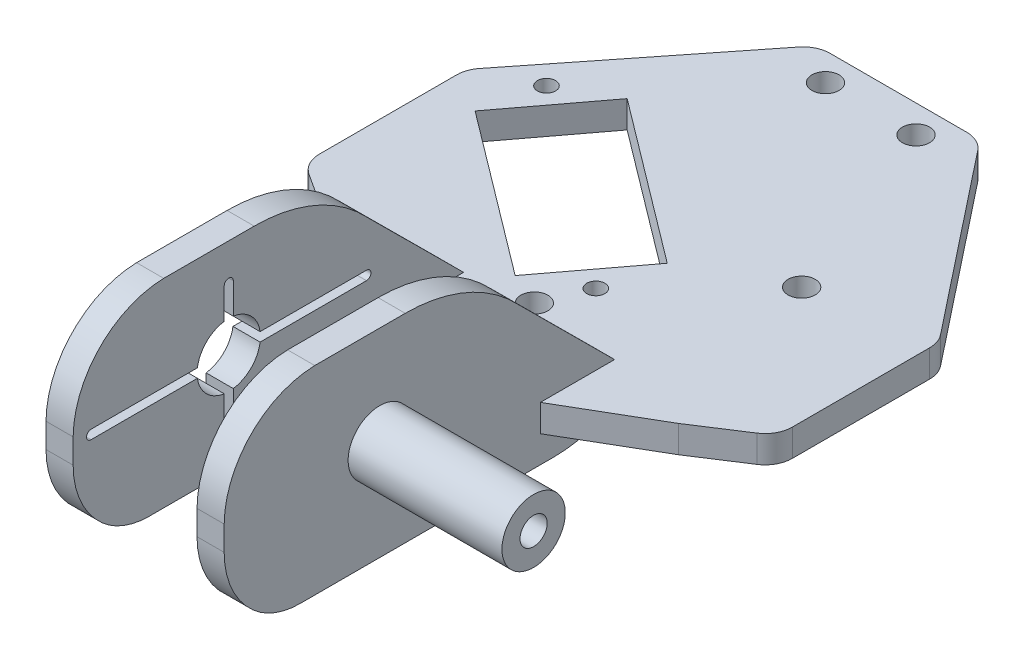
SolidWorks part; units mm, degrees
ref_plane "Front Plane" through (0, 0, 0) normal (0, 0, 1) x (1, 0, 0)
ref_plane "Top Plane" through (0, 0, 0) normal (0, 1, 0) x (1, 0, 0)
ref_plane "Right Plane" through (0, 0, 0) normal (1, 0, 0) x (0, 0, -1)
sketch "Sketch1" plane through (0, 0, 0) normal (0, 1, 0) x (1, 0, 0)
  line L7 (-4.1595, 37.5951) -> (4.2976, 37.5951)
  line L8 (-9.9025, 36.4566) -> (-20.3157, 23.2959) construction
  line L10 (0, 0) -> (0, -15.9475) construction
  line L12 (-9.9025, 36.4566) -> (-20.3157, 23.2959)
  line L15 (-20.9631, 21.4344) -> (-20.9631, -5.9026) construction
  line L16 (-19.4729, -6.2109) -> (-9.8452, -11.8182)
  line L19 (-9.8452, -11.8182) -> (-9.8452, -21.8182)
  line L22 (-9.8452, -21.8182) -> (-6.8452, -21.8182)
  line L23 (-6.8452, -21.8182) -> (-6.8452, -12.4305)
  line L24 (-6.8452, -12.4305) -> (6.8452, -12.4305)
  line L25 (-4.1595, 37.5951) -> (-7.5499, 37.5951)
  line L26 (4.1595, 37.5951) -> (1.3957, 42.8144)
  line L27 (1.3957, 42.8144) -> (0, 43.4367)
  line L28 (24.762, -2.7815) -> (19.4729, -6.2109)
  line L29 (26.1299, 14.9044) -> (26.1299, -0.2643)
  line L30 (18.8536, 25.1438) -> (25.4825, 16.7659)
  line L31 (-18.8536, 25.1438) -> (-25.4825, 16.7659)
  line L32 (-26.1299, 14.9044) -> (-26.1299, -0.2643)
  line L33 (-24.762, -2.7815) -> (-19.4729, -6.2109)
  line L34 (4.1595, 37.5951) -> (7.5499, 37.5951)
  line L35 (6.8452, -21.8182) -> (6.8452, -12.4305)
  line L36 (9.8452, -21.8182) -> (6.8452, -21.8182)
  line L37 (9.8452, -11.8182) -> (9.8452, -21.8182)
  line L38 (19.4729, -6.2109) -> (9.8452, -11.8182)
  line L39 (0, 0) -> (0, 47.8638) construction
  line L40 (-1.3957, 42.8144) -> (0, 43.4367)
  line L41 (-4.1595, 37.5951) -> (-1.3957, 42.8144)
  line L42 (9.9025, 36.4566) -> (20.3157, 23.2959)
  arc A1 (-7.5499, 37.5951) -> (-9.9025, 36.4566) centre (-7.5499, 34.5951) ccw construction
  circle A4 centre (-5.0017, 34.5359) radius 1.5 construction
  circle A8 centre (-5.0017, 34.5359) radius 1.5
  arc A11 (-7.5499, 37.5951) -> (-9.9025, 36.4566) centre (-7.5499, 34.5951) ccw
  arc A12 (-19.7137, -6.0547) -> (-19.4729, -6.2109) centre (-17.9631, -3.6185) ccw
  arc A14 (25.4825, 16.7659) -> (26.1299, 14.9044) centre (23.1299, 14.9044) cw
  arc A15 (26.1299, -0.2643) -> (24.762, -2.7815) centre (23.1299, -0.2643) cw
  arc A16 (19.7137, -6.0547) -> (19.4729, -6.2109) centre (17.9631, -3.6185) cw
  arc A17 (-26.1299, -0.2643) -> (-24.762, -2.7815) centre (-23.1299, -0.2643) ccw
  arc A18 (-25.4825, 16.7659) -> (-26.1299, 14.9044) centre (-23.1299, 14.9044) ccw
  arc A19 (7.5499, 37.5951) -> (9.9025, 36.4566) centre (7.5499, 34.5951) cw
  circle A20 centre (5.0017, 34.5359) radius 1.5
  point P28 (0.1548, -12.4305)
  point P33 (-20.9631, -5.343)
  point P37 (0, -12.4305)
  point P41 (0.1548, -12.4305)
  point P46 (26.1299, 15.9477)
  point P48 (26.1299, -1.8946)
  point P49 (-0.1548, -12.4305)
  point P50 (20.9631, -5.343)
  point P54 (-26.1299, -1.8946)
  point P57 (-26.1299, 15.9477)
  dimension "D1" = 3
  dimension "D3" = 3
  dimension "D4" = 10
extrude "Boss-Extrude2" add sketch "Sketch1" along normal blind 3 contours A11 L12 A12 L16 L19 L22 L23 A8 region at (0, 0, -10.32)
mirror "Mirror1" about plane through (0, 0, 0) normal (1, 0, 0) of "Boss-Extrude2"
sketch "Sketch3" plane through (9.8452, 0, 0) normal (1, 0, 0) x (0, 0, -1)
  line L0 (0, 0) -> (-5.4214, -2.0662)
  line L1 (-10.362, -2.9757) -> (-38.362, -2.9757)
  line L2 (-46.7647, 6.1171) -> (-46.7647, 8.8248)
  line L3 (-36.7549, 18.9944) -> (-26.7549, 18.9944)
  line L4 (-14.3131, 13.6377) -> (-3.6185, 3)
  line L5 (-3.6185, 3) -> (0, 0)
  line L6 (-11.8182, 3) -> (-11.8182, 0) construction
  arc A0 (-5.4214, -2.0662) -> (-10.362, -2.9757) centre (-10.362, 10.8976) cw
  arc A1 (-38.362, -2.9757) -> (-43.5481, -1.0139) centre (-38.362, 4.8597) cw
  arc A2 (-43.5481, -1.0139) -> (-46.7647, 6.1171) centre (-37.2518, 6.1171) cw
  circle A5 centre (-29.5682, 8.0684) radius 5 construction
  arc A7 (-26.7549, 18.9944) -> (-14.3131, 13.6377) centre (-26.7549, 1.8671) cw
  arc A8 (-36.7549, 18.9944) -> (-46.7647, 8.8248) centre (-36.4897, 8.7223) ccw
  dimension "D1" = 10
  dimension "D2" = 17.75
  dimension "D3" = 28
  dimension "D4" = 10
extrude "Boss-Extrude3" add sketch "Sketch3" against normal blind 3
sketch "Sketch4" plane through (9.8452, 0, 0) normal (1, 0, 0) x (0, 0, -1)
  circle A0 centre (-29.5682, 8.0684) radius 5
mirror "Mirror2" about plane through (0, 0, 0) normal (1, 0, 0) of "Boss-Extrude3"
extrude "Cut-Extrude1" cut sketch "Sketch4" against normal up to surface (3 mm away) rebuild error yes
sketch "Sketch5" plane through (-9.8452, 0, 0) normal (-1, 0, 0) x (0, 0, 1)
  line L0 (14.3482, 8.0684) -> (44.7882, 8.0684) construction
  line L1 (14.3482, 8.5684) -> (44.7882, 8.5684)
  line L2 (14.3482, 7.5684) -> (44.7882, 7.5684)
  line L3 (29.5682, 1.2134) -> (29.5682, 14.9234) construction
  line L4 (29.0682, 1.2134) -> (29.0682, 14.9234)
  line L5 (30.0682, 1.2134) -> (30.0682, 14.9234)
  circle A0 centre (29.5682, 8.0684) radius 5 construction
  circle A1 centre (29.5682, 8.0684) radius 5 construction
  arc A2 (14.3482, 8.5684) -> (14.3482, 7.5684) centre (14.3482, 8.0684) ccw
  arc A3 (44.7882, 7.5684) -> (44.7882, 8.5684) centre (44.7882, 8.0684) ccw
  arc A4 (29.0682, 1.2134) -> (30.0682, 1.2134) centre (29.5682, 1.2134) ccw
  arc A5 (30.0682, 14.9234) -> (29.0682, 14.9234) centre (29.5682, 14.9234) ccw
  circle A6 centre (29.5682, 8.0684) radius 3.5
  point P5 (29.5682, 8.0684)
  point P11 (29.5682, 8.0684)
  dimension "D1" = 0.5
  dimension "D2" = 0.5
  dimension "D5" = 10
  dimension "D6" = 7
  dimension "D3" = 30.44
  dimension "D4" = 13.71
extrude "Cut-Extrude2" cut sketch "Sketch5" against normal blind 3 contours L5 A6 L2 | L2 A6 L4 | L4 A6 L1 | L1 A6 L5 | L2 A3 L1 A2 | L5 A4 L4 A5 region at (-9.8452, 9.7725, 27.8641) region at (-9.8452, 6.3644, 27.8641) region at (-9.8452, 9.7725, 31.2723) region at (-9.8452, 6.3644, 31.2723)
sketch "Sketch7" plane through (0, 3, 0) normal (0, 1, 0) x (1, 0, 0)
  line L0 (-14.4326, 22.0478) -> (3.5367, 8.507)
  line L1 (3.5367, 8.507) -> (-3.6851, -1.0766)
  line L2 (-3.6851, -1.0766) -> (-21.6544, 12.4642)
  line L3 (-21.6544, 12.4642) -> (-14.4326, 22.0478)
  line L26 (-6.8452, -3.6185) -> (-6.8452, -12.4305)
  line L27 (-6.8452, -3.6185) -> (-6.8452, -12.4305)
  line L42 (6.8452, -3.6185) -> (9.8452, -3.6185)
  line L43 (6.8452, -3.6185) -> (9.8452, -3.6185)
  line L44 (-9.9025, 36.4566) -> (-25.4825, 16.7659)
  line L45 (-9.9025, 36.4566) -> (-25.4825, 16.7659)
  line L46 (-19.4729, -6.2109) -> (-9.8452, -11.8182)
  line L47 (-19.4729, -6.2109) -> (-9.8452, -11.8182)
  line L48 (-9.8452, -11.8182) -> (-9.8452, -3.6185)
  line L50 (-9.8452, -11.8182) -> (-9.8452, -3.6185)
  line L52 (-24.762, -2.7815) -> (-19.4729, -6.2109)
  line L53 (-24.762, -2.7815) -> (-19.4729, -6.2109)
  line L54 (-9.8452, -3.6185) -> (-6.8452, -3.6185)
  line L55 (-9.8452, -3.6185) -> (-6.8452, -3.6185)
  line L56 (-26.1299, 14.9044) -> (-26.1299, -0.2643)
  line L57 (-26.1299, 14.9044) -> (-26.1299, -0.2643)
  line L62 (7.5499, 37.5951) -> (-7.5499, 37.5951)
  line L64 (7.5499, 37.5951) -> (-7.5499, 37.5951)
  line L66 (-6.8452, -12.4305) -> (6.8452, -12.4305)
  line L68 (-6.8452, -12.4305) -> (6.8452, -12.4305)
  line L70 (6.8452, -12.4305) -> (6.8452, -3.6185)
  line L72 (6.8452, -12.4305) -> (6.8452, -3.6185)
  line L74 (9.8452, -3.6185) -> (9.8452, -11.8182)
  line L76 (9.8452, -3.6185) -> (9.8452, -11.8182)
  line L78 (9.8452, -11.8182) -> (19.4729, -6.2109)
  line L80 (9.8452, -11.8182) -> (19.4729, -6.2109)
  line L82 (19.4729, -6.2109) -> (24.762, -2.7815)
  line L83 (19.4729, -6.2109) -> (24.762, -2.7815)
  line L84 (26.1299, -0.2643) -> (26.1299, 14.9044)
  line L85 (26.1299, -0.2643) -> (26.1299, 14.9044)
  line L86 (25.4825, 16.7659) -> (9.9025, 36.4566)
  line L87 (25.4825, 16.7659) -> (9.9025, 36.4566)
  circle A0 centre (-20.1199, 18.8207) radius 1
  circle A1 centre (2.0023, 2.1505) radius 1
  arc A3 (-7.5499, 37.5951) -> (-9.9025, 36.4566) centre (-7.5499, 34.5951) ccw
  arc A18 (-7.5499, 37.5951) -> (-9.9025, 36.4566) centre (-7.5499, 34.5951) ccw
  arc A19 (-25.4825, 16.7659) -> (-26.1299, 14.9044) centre (-23.1299, 14.9044) ccw
  arc A20 (-25.4825, 16.7659) -> (-26.1299, 14.9044) centre (-23.1299, 14.9044) ccw
  arc A22 (-26.1299, -0.2643) -> (-24.762, -2.7815) centre (-23.1299, -0.2643) ccw
  arc A24 (-26.1299, -0.2643) -> (-24.762, -2.7815) centre (-23.1299, -0.2643) ccw
  arc A25 (24.762, -2.7815) -> (26.1299, -0.2643) centre (23.1299, -0.2643) ccw
  arc A26 (24.762, -2.7815) -> (26.1299, -0.2643) centre (23.1299, -0.2643) ccw
  arc A27 (26.1299, 14.9044) -> (25.4825, 16.7659) centre (23.1299, 14.9044) ccw
  arc A28 (26.1299, 14.9044) -> (25.4825, 16.7659) centre (23.1299, 14.9044) ccw
  arc A29 (9.9025, 36.4566) -> (7.5499, 37.5951) centre (7.5499, 34.5951) ccw
  arc A30 (9.9025, 36.4566) -> (7.5499, 37.5951) centre (7.5499, 34.5951) ccw
  dimension "D2" = 12
  dimension "D3" = 22.5
  dimension "D1" = 0
sketch "Sketch8" plane through (0, 3, 0) normal (0, 1, 0) x (1, 0, 0)
  line L0 (-14.4326, 22.0478) -> (3.5367, 8.507) construction
  line L1 (3.5367, 8.507) -> (-3.6851, -1.0766) construction
  line L2 (-3.6851, -1.0766) -> (-21.6544, 12.4642) construction
  line L3 (-21.6544, 12.4642) -> (-14.4326, 22.0478) construction
  line L4 (-14.4326, 22.0478) -> (3.5367, 8.507)
  line L5 (3.5367, 8.507) -> (-3.6851, -1.0766)
  line L6 (-3.6851, -1.0766) -> (-21.6544, 12.4642)
  line L7 (-21.6544, 12.4642) -> (-14.4326, 22.0478)
  line L28 (-24.762, -2.7815) -> (-19.4729, -6.2109)
  line L30 (-6.8452, -3.6185) -> (-6.8452, -12.4305)
  line L31 (-6.8452, -3.6185) -> (-6.8452, -12.4305)
  line L44 (-24.762, -2.7815) -> (-19.4729, -6.2109)
  line L48 (6.8452, -3.6185) -> (9.8452, -3.6185)
  line L49 (6.8452, -3.6185) -> (9.8452, -3.6185)
  line L50 (-9.9025, 36.4566) -> (-25.4825, 16.7659)
  line L51 (-9.9025, 36.4566) -> (-25.4825, 16.7659)
  line L52 (-26.1299, 14.9044) -> (-26.1299, -0.2643)
  line L53 (-26.1299, 14.9044) -> (-26.1299, -0.2643)
  line L54 (-19.4729, -6.2109) -> (-9.8452, -11.8182)
  line L55 (-19.4729, -6.2109) -> (-9.8452, -11.8182)
  line L56 (-9.8452, -11.8182) -> (-9.8452, -3.6185)
  line L57 (-9.8452, -11.8182) -> (-9.8452, -3.6185)
  line L58 (-9.8452, -3.6185) -> (-6.8452, -3.6185)
  line L59 (-9.8452, -3.6185) -> (-6.8452, -3.6185)
  line L64 (7.5499, 37.5951) -> (-7.5499, 37.5951)
  line L66 (7.5499, 37.5951) -> (-7.5499, 37.5951)
  line L68 (-6.8452, -12.4305) -> (6.8452, -12.4305)
  line L70 (-6.8452, -12.4305) -> (6.8452, -12.4305)
  line L72 (6.8452, -12.4305) -> (6.8452, -3.6185)
  line L74 (6.8452, -12.4305) -> (6.8452, -3.6185)
  line L76 (9.8452, -3.6185) -> (9.8452, -11.8182)
  line L78 (9.8452, -3.6185) -> (9.8452, -11.8182)
  line L80 (9.8452, -11.8182) -> (19.4729, -6.2109)
  line L82 (9.8452, -11.8182) -> (19.4729, -6.2109)
  line L84 (19.4729, -6.2109) -> (24.762, -2.7815)
  line L85 (19.4729, -6.2109) -> (24.762, -2.7815)
  line L86 (26.1299, -0.2643) -> (26.1299, 14.9044)
  line L87 (26.1299, -0.2643) -> (26.1299, 14.9044)
  line L88 (25.4825, 16.7659) -> (9.9025, 36.4566)
  line L89 (25.4825, 16.7659) -> (9.9025, 36.4566)
  circle A0 centre (-20.1199, 18.8207) radius 1 construction
  circle A1 centre (2.0023, 2.1505) radius 1 construction
  circle A2 centre (-20.1199, 18.8207) radius 1
  circle A3 centre (2.0023, 2.1505) radius 1
  arc A5 (-7.5499, 37.5951) -> (-9.9025, 36.4566) centre (-7.5499, 34.5951) ccw
  arc A18 (-7.5499, 37.5951) -> (-9.9025, 36.4566) centre (-7.5499, 34.5951) ccw
  arc A19 (-25.4825, 16.7659) -> (-26.1299, 14.9044) centre (-23.1299, 14.9044) ccw
  arc A20 (-25.4825, 16.7659) -> (-26.1299, 14.9044) centre (-23.1299, 14.9044) ccw
  arc A21 (-26.1299, -0.2643) -> (-24.762, -2.7815) centre (-23.1299, -0.2643) ccw
  arc A22 (-26.1299, -0.2643) -> (-24.762, -2.7815) centre (-23.1299, -0.2643) ccw
  arc A23 (24.762, -2.7815) -> (26.1299, -0.2643) centre (23.1299, -0.2643) ccw
  arc A24 (24.762, -2.7815) -> (26.1299, -0.2643) centre (23.1299, -0.2643) ccw
  arc A25 (26.1299, 14.9044) -> (25.4825, 16.7659) centre (23.1299, 14.9044) ccw
  arc A26 (26.1299, 14.9044) -> (25.4825, 16.7659) centre (23.1299, 14.9044) ccw
  arc A27 (9.9025, 36.4566) -> (7.5499, 37.5951) centre (7.5499, 34.5951) ccw
  arc A28 (9.9025, 36.4566) -> (7.5499, 37.5951) centre (7.5499, 34.5951) ccw
  dimension "D1" = 0
sketch "Sketch9" plane through (0, 3, 0) normal (0, 1, 0) x (1, 0, 0)
  line L0 (3.5367, 8.507) -> (-3.6851, -1.0766) construction
  line L1 (-14.4326, 22.0478) -> (3.5367, 8.507) construction
  line L2 (-3.6851, -1.0766) -> (-21.6544, 12.4642) construction
  line L3 (-21.6544, 12.4642) -> (-14.4326, 22.0478) construction
  line L4 (3.5367, 8.507) -> (-3.6851, -1.0766)
  line L5 (-14.4326, 22.0478) -> (3.5367, 8.507)
  line L6 (-3.6851, -1.0766) -> (-21.6544, 12.4642)
  line L7 (-21.6544, 12.4642) -> (-14.4326, 22.0478)
  line L28 (-24.762, -2.7815) -> (-19.4729, -6.2109)
  line L30 (-6.8452, -3.6185) -> (-6.8452, -12.4305)
  line L31 (-6.8452, -3.6185) -> (-6.8452, -12.4305)
  line L44 (-24.762, -2.7815) -> (-19.4729, -6.2109)
  line L48 (6.8452, -3.6185) -> (9.8452, -3.6185)
  line L49 (6.8452, -3.6185) -> (9.8452, -3.6185)
  line L50 (-9.9025, 36.4566) -> (-25.4825, 16.7659)
  line L51 (-26.1299, 14.9044) -> (-26.1299, -0.2643)
  line L52 (-19.4729, -6.2109) -> (-9.8452, -11.8182)
  line L53 (-19.4729, -6.2109) -> (-9.8452, -11.8182)
  line L54 (-9.8452, -11.8182) -> (-9.8452, -3.6185)
  line L55 (-9.8452, -11.8182) -> (-9.8452, -3.6185)
  line L56 (-9.8452, -3.6185) -> (-6.8452, -3.6185)
  line L57 (-9.8452, -3.6185) -> (-6.8452, -3.6185)
  line L62 (7.5499, 37.5951) -> (-7.5499, 37.5951)
  line L63 (7.5499, 37.5951) -> (-7.5499, 37.5951)
  line L64 (-6.8452, -12.4305) -> (6.8452, -12.4305)
  line L65 (-6.8452, -12.4305) -> (6.8452, -12.4305)
  line L66 (6.8452, -12.4305) -> (6.8452, -3.6185)
  line L67 (6.8452, -12.4305) -> (6.8452, -3.6185)
  line L68 (9.8452, -3.6185) -> (9.8452, -11.8182)
  line L69 (9.8452, -3.6185) -> (9.8452, -11.8182)
  line L70 (9.8452, -11.8182) -> (19.4729, -6.2109)
  line L71 (9.8452, -11.8182) -> (19.4729, -6.2109)
  line L72 (19.4729, -6.2109) -> (24.762, -2.7815)
  line L73 (19.4729, -6.2109) -> (24.762, -2.7815)
  line L74 (26.1299, -0.2643) -> (26.1299, 14.9044)
  line L75 (26.1299, -0.2643) -> (26.1299, 14.9044)
  line L76 (25.4825, 16.7659) -> (9.9025, 36.4566)
  line L77 (25.4825, 16.7659) -> (9.9025, 36.4566)
  circle A0 centre (2.0023, 2.1505) radius 1 construction
  circle A1 centre (-20.1199, 18.8207) radius 1 construction
  circle A2 centre (2.0023, 2.1505) radius 1
  circle A4 centre (-20.1199, 18.8207) radius 1
  arc A6 (-7.5499, 37.5951) -> (-9.9025, 36.4566) centre (-7.5499, 34.5951) ccw
  arc A21 (-7.5499, 37.5951) -> (-9.9025, 36.4566) centre (-7.5499, 34.5951) ccw
  arc A22 (-25.4825, 16.7659) -> (-26.1299, 14.9044) centre (-23.1299, 14.9044) ccw
  arc A23 (-26.1299, -0.2643) -> (-24.762, -2.7815) centre (-23.1299, -0.2643) ccw
  arc A24 (-26.1299, -0.2643) -> (-24.762, -2.7815) centre (-23.1299, -0.2643) ccw
  arc A25 (24.762, -2.7815) -> (26.1299, -0.2643) centre (23.1299, -0.2643) ccw
  arc A26 (24.762, -2.7815) -> (26.1299, -0.2643) centre (23.1299, -0.2643) ccw
  arc A27 (26.1299, 14.9044) -> (25.4825, 16.7659) centre (23.1299, 14.9044) ccw
  arc A28 (26.1299, 14.9044) -> (25.4825, 16.7659) centre (23.1299, 14.9044) ccw
  arc A29 (9.9025, 36.4566) -> (7.5499, 37.5951) centre (7.5499, 34.5951) ccw
  arc A30 (9.9025, 36.4566) -> (7.5499, 37.5951) centre (7.5499, 34.5951) ccw
  dimension "D1" = 0
sketch "Sketch10" plane through (0, 3, 0) normal (0, 1, 0) x (1, 0, 0)
  line L16 (-6.8452, -3.6185) -> (-6.8452, -12.4305)
  line L17 (-6.8452, -12.4305) -> (6.8452, -12.4305)
  line L18 (6.8452, -12.4305) -> (6.8452, -3.6185)
  line L19 (6.8452, -3.6185) -> (9.8452, -3.6185)
  line L20 (9.8452, -3.6185) -> (9.8452, -11.8182)
  line L21 (9.8452, -11.8182) -> (19.4729, -6.2109)
  line L22 (19.4729, -6.2109) -> (24.762, -2.7815)
  line L23 (26.1299, -0.2643) -> (26.1299, 14.9044)
  line L24 (25.4825, 16.7659) -> (9.9025, 36.4566)
  line L25 (7.5499, 37.5951) -> (-7.5499, 37.5951)
  line L26 (-9.9025, 36.4566) -> (-25.4825, 16.7659)
  line L27 (-26.1299, 14.9044) -> (-26.1299, -0.2643)
  line L28 (-24.762, -2.7815) -> (-19.4729, -6.2109)
  line L29 (-19.4729, -6.2109) -> (-9.8452, -11.8182)
  line L30 (-9.8452, -11.8182) -> (-9.8452, -3.6185)
  line L31 (-9.8452, -3.6185) -> (-6.8452, -3.6185)
  line L32 (-6.8452, -3.6185) -> (-6.8452, -12.4305)
  line L33 (-6.8452, -12.4305) -> (6.8452, -12.4305)
  line L34 (6.8452, -12.4305) -> (6.8452, -3.6185)
  line L35 (6.8452, -3.6185) -> (9.8452, -3.6185)
  line L36 (9.8452, -3.6185) -> (9.8452, -11.8182)
  line L37 (9.8452, -11.8182) -> (19.4729, -6.2109)
  line L38 (19.4729, -6.2109) -> (24.762, -2.7815)
  line L39 (26.1299, -0.2643) -> (26.1299, 14.9044)
  line L40 (25.4825, 16.7659) -> (9.9025, 36.4566)
  line L41 (7.5499, 37.5951) -> (-7.5499, 37.5951)
  line L42 (-9.9025, 36.4566) -> (-25.4825, 16.7659)
  line L43 (-26.1299, 14.9044) -> (-26.1299, -0.2643)
  line L44 (-24.762, -2.7815) -> (-19.4729, -6.2109)
  line L45 (-19.4729, -6.2109) -> (-9.8452, -11.8182)
  line L46 (-9.8452, -11.8182) -> (-9.8452, -3.6185)
  line L47 (-9.8452, -3.6185) -> (-6.8452, -3.6185)
  arc A6 (24.762, -2.7815) -> (26.1299, -0.2643) centre (23.1299, -0.2643) ccw
  arc A7 (26.1299, 14.9044) -> (25.4825, 16.7659) centre (23.1299, 14.9044) ccw
  arc A8 (9.9025, 36.4566) -> (7.5499, 37.5951) centre (7.5499, 34.5951) ccw
  arc A9 (-7.5499, 37.5951) -> (-9.9025, 36.4566) centre (-7.5499, 34.5951) ccw
  arc A10 (-25.4825, 16.7659) -> (-26.1299, 14.9044) centre (-23.1299, 14.9044) ccw
  arc A11 (-26.1299, -0.2643) -> (-24.762, -2.7815) centre (-23.1299, -0.2643) ccw
  arc A12 (24.762, -2.7815) -> (26.1299, -0.2643) centre (23.1299, -0.2643) ccw
  arc A13 (26.1299, 14.9044) -> (25.4825, 16.7659) centre (23.1299, 14.9044) ccw
  arc A14 (9.9025, 36.4566) -> (7.5499, 37.5951) centre (7.5499, 34.5951) ccw
  arc A15 (-7.5499, 37.5951) -> (-9.9025, 36.4566) centre (-7.5499, 34.5951) ccw
  arc A16 (-25.4825, 16.7659) -> (-26.1299, 14.9044) centre (-23.1299, 14.9044) ccw
  arc A17 (-26.1299, -0.2643) -> (-24.762, -2.7815) centre (-23.1299, -0.2643) ccw
  dimension "D1" = 0
extrude "Cut-Extrude3" cut sketch "Sketch9" against normal blind 10 contours L7 L6 L4 L5 | A4 | A2 region at (-9.0588, 3, -10.4856) region at (2.0023, 3, -2.1505) region at (-20.1199, 3, -18.8207)
sketch "Sketch16" plane through (0, 3, 0) normal (0, 1, 0) x (1, 0, 0)
  circle A0 centre (13.2517, 13.6459) radius 1.5
  circle A1 centre (5.0017, 34.5359) radius 1.5 construction
  dimension "D1" = 3
  dimension "D2" = 20.89
  dimension "D3" = 8.25
extrude "Cut-Extrude4" cut sketch "Sketch16" against normal blind 10
sketch "Sketch18" plane through (6.8452, 0, 0) normal (-1, 0, 0) x (0, 0, 1)
  circle A0 centre (29.5682, 8.0684) radius 3.5
  dimension "D1" = 7
sketch "Sketch19" plane through (0, 3, 0) normal (0, 1, 0) x (1, 0, 0)
  circle A0 centre (0, -2.643) radius 1.5
  dimension "D1" = 3
extrude "Cut-Extrude6" cut sketch "Sketch19" against normal blind 10
extrude "Boss-Extrude4" add sketch "Sketch18" against normal blind 20
sketch "Sketch20" plane through (26.8452, 0, 0) normal (1, 0, 0) x (0, 0, -1)
  circle A0 centre (-29.5682, 8.0684) radius 1.5
  dimension "D1" = 3
extrude "Cut-Extrude7" cut sketch "Sketch20" against normal blind 12
